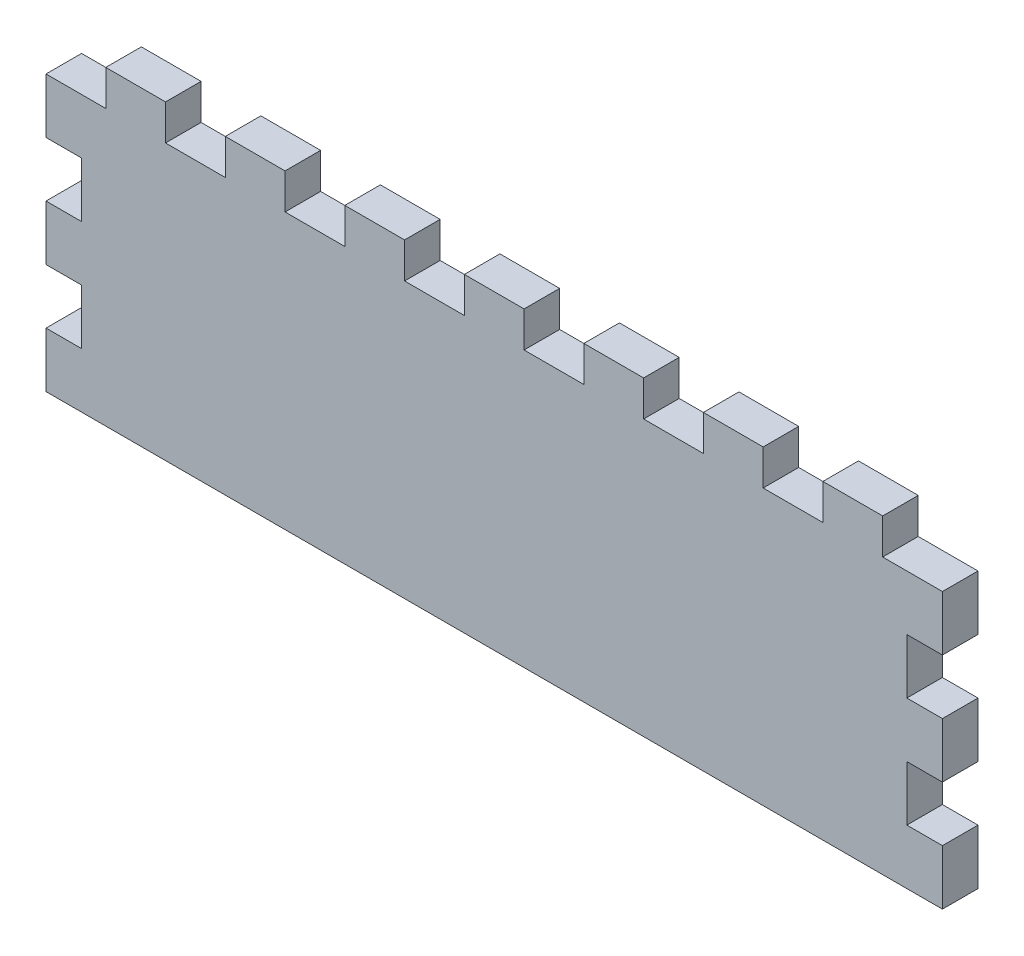
SolidWorks part; units mm, degrees
material "Acrylic (Medium-high impact)"
ref_plane "Front Plane" through (0, 0, 0) normal (0, 0, 1) x (1, 0, 0)
ref_plane "Top Plane" through (0, 0, 0) normal (0, 1, 0) x (1, 0, 0)
ref_plane "Right Plane" through (0, 0, 0) normal (1, 0, 0) x (0, 0, -1)
sketch "Sketch1" plane through (0, 0, 0) normal (0, 0, 1) x (1, 0, 0)
  line L1 (-40, -40) -> (40, -40)
  line L2 (-40, -40) -> (-40, 40)
  line L3 (-40, 40) -> (40, 40)
  line L4 (40, -40) -> (40, 40)
  line L5 (-40, -40) -> (40, 40) construction
  line L6 (-40, 40) -> (40, -40) construction
  point P0 (0, 0)
  dimension "D1" = 80
  dimension "D2" = 80
extrude "Boss-Extrude1" add sketch "Sketch1" along normal blind 3.175
sketch "Sketch2" plane through (0, 0, 3.175) normal (0, 0, 1) x (1, 0, 0)
  line L0 (0, 0) -> (-50000, 0) construction
  line L1 (-40, 40) -> (-40, -40) construction
  line L2 (-40, -36.825) -> (-34.6667, -36.825)
  line L3 (-34.6667, -36.825) -> (-34.6667, -40)
  line L5 (-40, 36.825) -> (-34.6667, 36.825)
  line L6 (-40, -36.825) -> (-40, -40)
  line L7 (-40, -40) -> (-34.6667, -40)
  line L8 (-34.6667, -40) -> (-40, -40)
  line L9 (-34.6667, -40) -> (-40, -40)
  line L10 (-29.3333, -36.825) -> (-29.3333, -40)
  line L11 (-29.3333, -36.825) -> (-24, -36.825)
  line L13 (-24, -36.825) -> (-24, -40)
  line L15 (-18.6667, -36.825) -> (-18.6667, -40)
  line L16 (-18.6667, -36.825) -> (-13.3333, -36.825)
  line L17 (-18.6667, -40) -> (-13.3333, -40)
  line L18 (-13.3333, -36.825) -> (-13.3333, -40)
  line L20 (-8, -36.825) -> (-8, -40)
  line L21 (-8, -36.825) -> (-2.6667, -36.825)
  line L22 (-8, -40) -> (-2.6667, -40)
  line L23 (-2.6667, -36.825) -> (-2.6667, -40)
  line L25 (2.6667, -36.825) -> (2.6667, -40)
  line L26 (2.6667, -36.825) -> (8, -36.825)
  line L27 (2.6667, -40) -> (8, -40)
  line L28 (8, -36.825) -> (8, -40)
  line L29 (40, 36.825) -> (40, 40)
  line L30 (13.3333, -36.825) -> (13.3333, -40)
  line L31 (13.3333, -36.825) -> (18.6667, -36.825)
  line L32 (13.3333, -40) -> (18.6667, -40)
  line L33 (18.6667, -36.825) -> (18.6667, -40)
  line L34 (34.6667, 40) -> (40, 40)
  line L35 (24, -36.825) -> (24, -40)
  line L36 (24, -36.825) -> (29.3333, -36.825)
  line L37 (24, -40) -> (29.3333, -40)
  line L38 (29.3333, -36.825) -> (29.3333, -40)
  line L39 (34.6667, 36.825) -> (40, 36.825)
  line L40 (34.6667, -36.825) -> (34.6667, -40)
  line L41 (34.6667, -36.825) -> (40, -36.825)
  line L42 (34.6667, -40) -> (40, -40)
  line L43 (40, -36.825) -> (40, -40)
  line L44 (34.6667, 36.825) -> (34.6667, 40)
  line L45 (-40, -36.825) -> (-34.6667, -36.825)
  line L46 (29.3333, 36.825) -> (29.3333, 40)
  line L47 (24, 40) -> (29.3333, 40)
  line L49 (24, 36.825) -> (29.3333, 36.825)
  line L51 (24, 36.825) -> (24, 40)
  line L53 (18.6667, 36.825) -> (18.6667, 40)
  line L54 (13.3333, 40) -> (18.6667, 40)
  line L55 (13.3333, 36.825) -> (18.6667, 36.825)
  line L56 (13.3333, 36.825) -> (13.3333, 40)
  line L57 (8, 36.825) -> (8, 40)
  line L58 (2.6667, 40) -> (8, 40)
  line L59 (2.6667, 36.825) -> (8, 36.825)
  line L60 (40, -31.915) -> (40, -36.825)
  line L61 (-36.825, -31.915) -> (-40, -31.915)
  line L62 (-36.825, -27.005) -> (-36.825, -31.915)
  line L63 (-40, -27.005) -> (-36.825, -27.005)
  line L64 (-40, -22.095) -> (-40, -27.005)
  line L65 (-36.825, -22.095) -> (-40, -22.095)
  line L66 (-36.825, -17.185) -> (-36.825, -22.095)
  line L68 (2.6667, 36.825) -> (2.6667, 40)
  line L69 (-2.6667, 36.825) -> (-2.6667, 40)
  line L70 (-8, 40) -> (-2.6667, 40)
  line L71 (-8, 36.825) -> (-2.6667, 36.825)
  line L72 (-8, 36.825) -> (-8, 40)
  line L73 (-13.3333, 36.825) -> (-13.3333, 40)
  line L74 (-18.6667, 40) -> (-13.3333, 40)
  line L75 (-18.6667, 36.825) -> (-13.3333, 36.825)
  line L76 (-18.6667, 36.825) -> (-18.6667, 40)
  line L77 (-24, 36.825) -> (-24, 40)
  line L78 (-29.3333, 36.825) -> (-24, 36.825)
  line L79 (-29.3333, 36.825) -> (-29.3333, 40)
  line L80 (-34.6667, 40) -> (-40, 40)
  line L81 (-34.6667, 40) -> (-40, 40)
  line L82 (-40, 40) -> (-34.6667, 40)
  line L83 (-40, 36.825) -> (-40, 40)
  line L84 (-34.6667, 36.825) -> (-34.6667, 40)
  line L85 (-40, 36.825) -> (-34.6667, 36.825)
  line L86 (40, 36.825) -> (40, 31.915)
  line L88 (40, 31.915) -> (36.825, 31.915)
  line L89 (36.825, 31.915) -> (36.825, 27.005)
  line L90 (36.825, 27.005) -> (40, 27.005)
  line L91 (40, 27.005) -> (40, 22.095)
  line L92 (40, 22.095) -> (36.825, 22.095)
  line L93 (36.825, 22.095) -> (36.825, 17.185)
  line L94 (36.825, 17.185) -> (40, 17.185)
  line L95 (40, 17.185) -> (40, 12.275)
  line L96 (40, 12.275) -> (36.825, 12.275)
  line L97 (36.825, 12.275) -> (36.825, 7.365)
  line L98 (36.825, 7.365) -> (40, 7.365)
  line L99 (40, 7.365) -> (40, 2.455)
  line L100 (40, 2.455) -> (36.825, 2.455)
  line L101 (36.825, 2.455) -> (36.825, -2.455)
  line L102 (36.825, -2.455) -> (40, -2.455)
  line L103 (40, -2.455) -> (40, -7.365)
  line L104 (40, -7.365) -> (36.825, -7.365)
  line L105 (36.825, -7.365) -> (36.825, -12.275)
  line L106 (36.825, -12.275) -> (40, -12.275)
  line L107 (40, -12.275) -> (40, -17.185)
  line L108 (40, -17.185) -> (36.825, -17.185)
  line L109 (36.825, -17.185) -> (36.825, -22.095)
  line L110 (36.825, -22.095) -> (40, -22.095)
  line L111 (40, -22.095) -> (40, -27.005)
  line L112 (40, -27.005) -> (36.825, -27.005)
  line L113 (36.825, -27.005) -> (36.825, -31.915)
  line L114 (36.825, -31.915) -> (40, -31.915)
  line L115 (0, 0) -> (0, 50000) construction
  line L116 (-40, 40) -> (-40, -40) construction
  line L117 (40, 40) -> (-40, 40) construction
  line L118 (-40, -17.185) -> (-36.825, -17.185)
  line L119 (-40, -12.275) -> (-40, -17.185)
  line L120 (-36.825, -12.275) -> (-40, -12.275)
  line L121 (-36.825, -7.365) -> (-36.825, -12.275)
  line L122 (-40, -7.365) -> (-36.825, -7.365)
  line L123 (-40, -2.455) -> (-40, -7.365)
  line L124 (-36.825, -2.455) -> (-40, -2.455)
  line L125 (-36.825, 2.455) -> (-36.825, -2.455)
  line L126 (-40, 2.455) -> (-36.825, 2.455)
  line L127 (-40, 7.365) -> (-40, 2.455)
  line L128 (-36.825, 7.365) -> (-40, 7.365)
  line L129 (-36.825, 12.275) -> (-36.825, 7.365)
  line L130 (-40, 12.275) -> (-36.825, 12.275)
  line L131 (-40, 17.185) -> (-40, 12.275)
  line L132 (-36.825, 17.185) -> (-40, 17.185)
  line L133 (-36.825, 22.095) -> (-36.825, 17.185)
  line L134 (-40, 22.095) -> (-36.825, 22.095)
  line L135 (-40, 27.005) -> (-40, 22.095)
  line L136 (-36.825, 27.005) -> (-40, 27.005)
  line L137 (-36.825, 31.915) -> (-36.825, 27.005)
  line L138 (-40, 31.915) -> (-36.825, 31.915)
  line L139 (-40, 36.825) -> (-40, 31.915)
  line L140 (-40, -31.915) -> (-40, -36.825)
  line L141 (34.6667, 40) -> (29.3333, 40)
  line L142 (24, 40) -> (18.6667, 40)
  line L143 (13.3333, 40) -> (8, 40)
  line L144 (2.6667, 40) -> (-2.6667, 40)
  line L145 (-8, 40) -> (-13.3333, 40)
  line L146 (-18.6667, 40) -> (-24, 40)
  line L147 (-29.3333, 40) -> (-34.6667, 40)
  point P111 (0, 40)
  line M50 (-40, 40) -> (-40, -40)
  line M51 (-40, -40) -> (40, -40)
  dimension "D2" = 3.175
  dimension "D5" = 3.175
extrude "Cut-Extrude1" cut sketch "Sketch2" against normal through all flip side to cut contours L138 L137 L136 L134 L133 L132 L130 L129 L128 L126 L125 L124 L122 L121 L120 L118 L66 L65 L63 L62 L61 L2 L3 L10 L11 L13 L15 L16 L18 L20 L21 L23 L25 L26 L28 L30 L31 L33 M50 M51 region at (0, 0, 3.175)
sketch "Sketch3" plane through (0, 0, 0) normal (0, 0, -1) x (-1, 0, 0)
  line L0 (34.6667, -40) -> (29.3333, -40) construction
  line L1 (-40, 12.275) -> (40, 12.275)
  line L2 (-40, 12.275) -> (-40, -40)
  line L3 (-40, -40) -> (40, -40)
  line L4 (40, 12.275) -> (40, -40)
  dimension "D1" = 80
  dimension "D2" = 0
extrude "Cut-Extrude2" cut sketch "Sketch3" against normal through all
